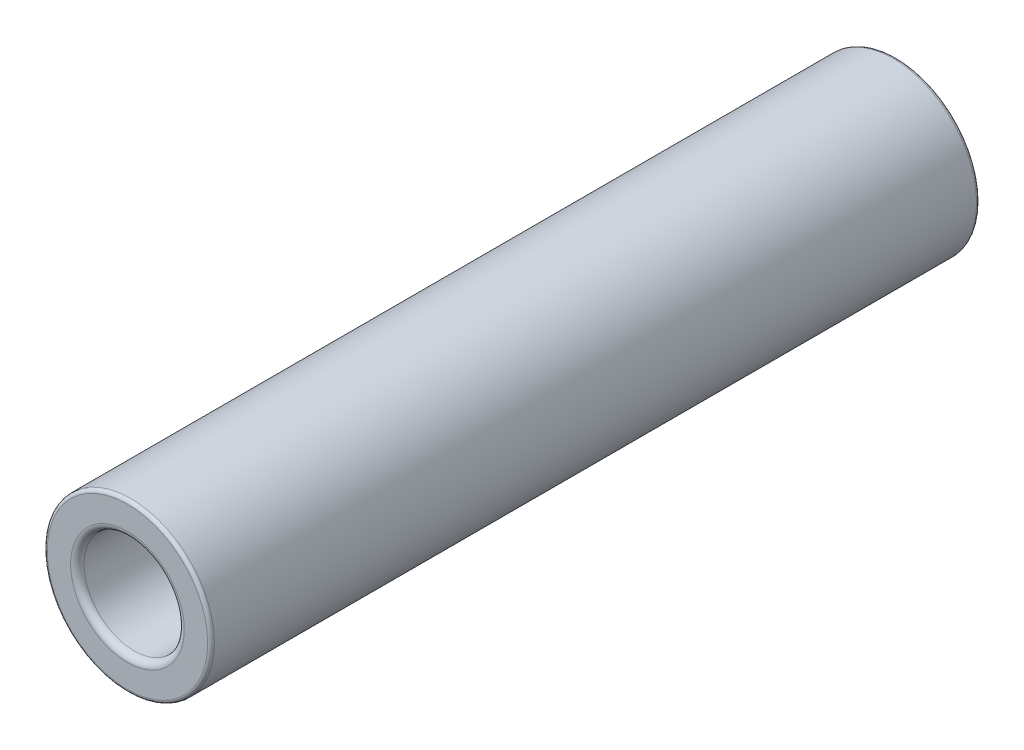
SolidWorks part; units mm, degrees
ref_plane "Alzado" through (0, 0, 0) normal (0, 0, 1) x (1, 0, 0)
ref_plane "Planta" through (0, 0, 0) normal (0, 1, 0) x (1, 0, 0)
ref_plane "Vista lateral" through (0, 0, 0) normal (1, 0, 0) x (0, 0, -1)
sketch "Croquis1" plane through (0, 0, 0) normal (0, 0, 1) x (1, 0, 0)
  circle A0 centre (0, 0) radius 1.5
  circle A1 centre (0, 0) radius 2.5
  dimension "D1" = 3
  dimension "D2" = 5
extrude "Saliente-Extruir2" add sketch "Croquis1" along normal blind 23
fillet "Redondeo5" radius 0.1 2 edges at (2.5, 0, 0) (2.5, 0, 23)
fillet "Redondeo6" radius 0.2 2 edges at (1.5, 0, 0) (1.5, 0, 23)
